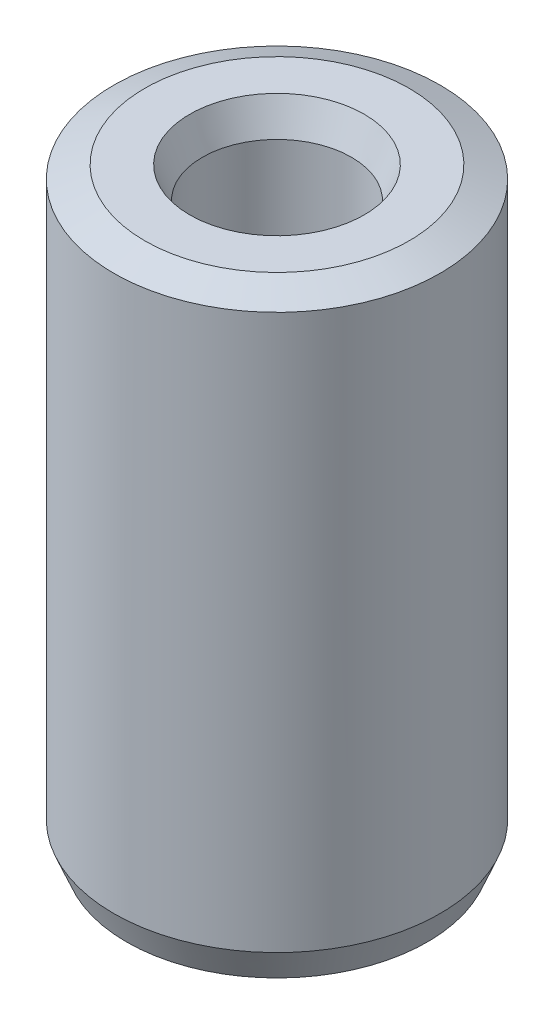
SolidWorks part; units mm, degrees
ref_plane "Front Plane" through (0, 0, 0) normal (0, 0, 1) x (1, 0, 0)
ref_plane "Top Plane" through (0, 0, 0) normal (0, 1, 0) x (1, 0, 0)
ref_plane "Right Plane" through (0, 0, 0) normal (1, 0, 0) x (0, 0, -1)
sketch "Sketch1" plane through (0, 0, 0) normal (0, 1, 0) x (1, 0, 0)
  circle A0 centre (0, 0) radius 50
  dimension "SLEEVE_OD" = 100
extrude "Boss-Extrude1" add sketch "Sketch1" along normal blind 183.3241
sketch "Sketch2" plane through (0, 0, 0) normal (0, 1, 0) x (1, 0, 0)
  circle A0 centre (0, 0) radius 22.8628
  dimension "BORE_D" = 45.7257
extrude "Cut-Extrude1" cut sketch "Sketch2" along normal through all
chamfer "Chamfer1" distance 3.8819 angle 67.745 4 edges at (0, 183.3241, 22.8628) (0, 0, 22.8628) (0, 0, 50) (0, 183.3241, 50) first distance on face at (0, 183.3241, 22.8628) first distance on face at (0, 0, 22.8628) first distance on face at (0, 183.3241, 50)
